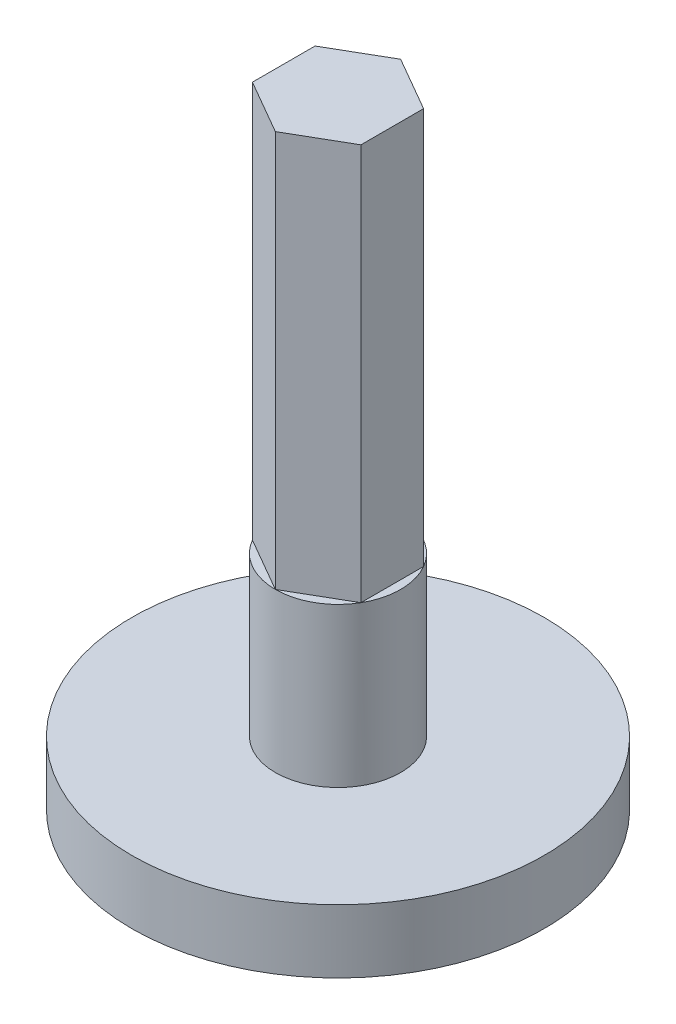
SolidWorks part; units mm, degrees
ref_plane "Alzado" through (0, 0, 0) normal (0, 0, 1) x (1, 0, 0)
ref_plane "Planta" through (0, 0, 0) normal (0, 1, 0) x (1, 0, 0)
ref_plane "Vista lateral" through (0, 0, 0) normal (1, 0, 0) x (0, 0, -1)
sketch "Croquis3" plane through (0, 0, 0) normal (0, 1, 0) x (1, 0, 0)
  circle A0 centre (0, 0) radius 13
  dimension "D1" = 26
extrude "Saliente-Extruir1" add sketch "Croquis3" along normal blind 4
sketch "Croquis4" plane through (0, 4, 0) normal (0, 1, 0) x (1, 0, 0)
  circle A0 centre (0, 0) radius 3.95
  dimension "D1" = 7.9
extrude "Saliente-Extruir2" add sketch "Croquis4" along normal blind 35
sketch "Croquis7" plane through (0, 0, 0) normal (0, -1, 0) x (1, 0, 0)
  circle A0 centre (0, 0) radius 12
  dimension "D1" = 24
sketch "Croquis12" plane through (0, 39, 0) normal (0, 1, 0) x (1, 0, 0)
  line L1 (0, 3.95) -> (-3.4208, 1.975)
  line L2 (-3.4208, 1.975) -> (-3.4208, -1.975)
  line L3 (-3.4208, -1.975) -> (0, -3.95)
  line L4 (0, -3.95) -> (3.4208, -1.975)
  line L5 (3.4208, -1.975) -> (3.4208, 1.975)
  line L6 (3.4208, 1.975) -> (0, 3.95)
  circle A0 centre (0, 0) radius 3.95 construction
  circle A1 centre (0, 0) radius 3.95 construction
  circle A2 centre (0, 0) radius 3.95 construction
extrude "Cortar-Extruir7" cut sketch "Croquis12" against normal blind 25 flip side to cut
